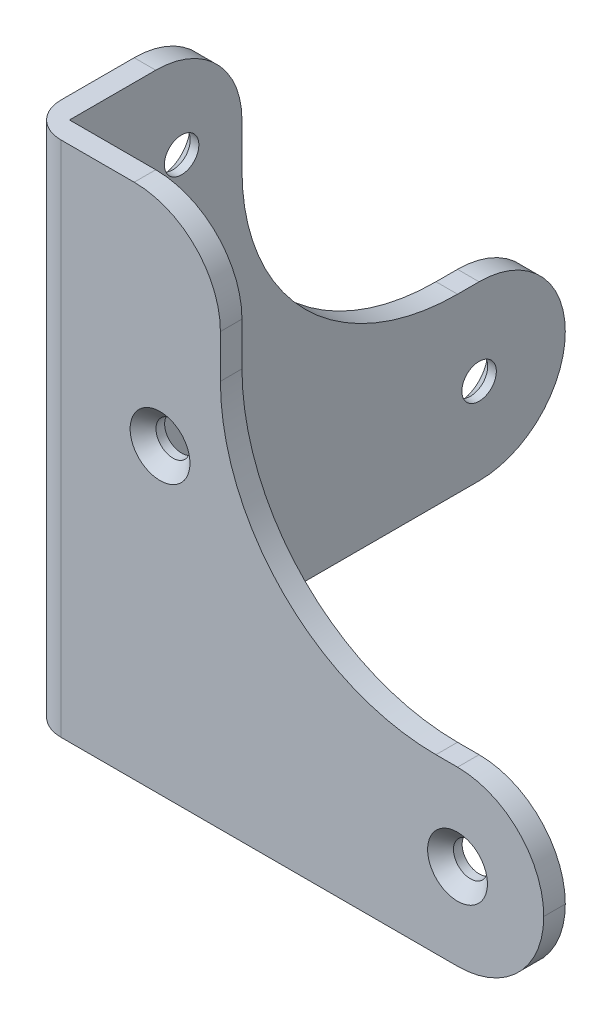
SolidWorks part; units mm, degrees
ref_plane "Front" through (0, 0, 0) normal (0, 0, 1) x (1, 0, 0)
ref_plane "Top" through (0, 0, 0) normal (0, 1, 0) x (1, 0, 0)
ref_plane "Right" through (0, 0, 0) normal (1, 0, 0) x (0, 0, -1)
sketch "Sketch1" plane through (0, 0, 0) normal (0, 1, 0) x (1, 0, 0)
  line L0 (0, 76.2) -> (0, 0)
  line L1 (0, 0) -> (76.2, 0)
  line L2 (76.2, 0) -> (76.2, 3.175)
  line L3 (76.2, 3.175) -> (3.175, 3.175)
  line L4 (3.175, 3.175) -> (3.175, 76.2)
  line L5 (3.175, 76.2) -> (0, 76.2)
  dimension "D1" = 3.175
  dimension "D2" = 76.2
extrude "Boss-Extrude1" add sketch "Sketch1" along normal blind 76.2
sketch "Sketch2" plane through (0, 0, -3.175) normal (0, 0, -1) x (-1, 0, 0)
  line L0 (-76.2, 0) -> (-3.175, 0) construction
  line L1 (-76.2, 76.2) -> (-28.575, 76.2)
  line L2 (-76.2, 76.2) -> (-76.2, 25.4)
  line L3 (-76.2, 25.4) -> (-28.575, 25.4)
  line L4 (-28.575, 76.2) -> (-28.575, 25.4)
  line L5 (-3.175, 76.2) -> (-3.175, 0) construction
  dimension "D1" = 25.4
  dimension "D2" = 25.4
extrude "Cut-Extrude1" cut sketch "Sketch2" against normal through all contours L4 L3 L2 L1
sketch "Sketch3" plane through (3.175, 0, 0) normal (1, 0, 0) x (0, 0, -1)
  line L0 (3.175, 76.2) -> (3.175, 0) construction
  line L1 (76.2, 76.2) -> (28.575, 76.2)
  line L2 (76.2, 76.2) -> (76.2, 25.4)
  line L3 (76.2, 25.4) -> (28.575, 25.4)
  line L4 (28.575, 76.2) -> (28.575, 25.4)
  line L5 (3.175, 0) -> (76.2, 0) construction
  dimension "D1" = 25.4
  dimension "D2" = 25.4
extrude "Cut-Extrude2" cut sketch "Sketch3" against normal through all
fillet "Fillet1" radius 5.08 1 edges at (0, 38.1, 0)
fillet "Fillet2" radius 12.7 6 edges at (1.5875, 76.2, -28.575) (1.5875, 25.4, -76.2) (1.5875, 0, -76.2) (76.2, 0, -1.5875) (76.2, 25.4, -1.5875) (28.575, 76.2, -1.5875)
sketch "Sketch4" plane through (0, 0, 0) normal (0, 0, 1) x (1, 0, 0)
  line L0 (28.575, 63.5) -> (28.575, 25.4) construction
  line L1 (5.08, 76.2) -> (15.875, 76.2) construction
  circle A0 centre (63.5, 12.7) radius 2.5
  arc A1 (76.2, 12.7) -> (63.5, 25.4) centre (63.5, 12.7) ccw construction
  circle A2 centre (19.685, 44.45) radius 2.5
  dimension "D1" = 5
  dimension "D2" = 8.89
  dimension "D3" = 31.75
extrude "Cut-Extrude3" cut sketch "Sketch4" against normal through all
sketch "Sketch5" plane through (0, 0, 0) normal (-1, 0, 0) x (0, 0, 1)
  line L0 (-28.575, 63.5) -> (-28.575, 25.4) construction
  line L1 (-15.875, 76.2) -> (-5.08, 76.2) construction
  circle A0 centre (-63.5, 12.7) radius 2.54
  circle A1 centre (-19.685, 63.5) radius 2.54
  arc A2 (-63.5, 25.4) -> (-76.2, 12.7) centre (-63.5, 12.7) ccw construction
  dimension "D1" = 8.89
  dimension "D2" = 12.7
  dimension "D3" = 5.08
extrude "Cut-Extrude4" cut sketch "Sketch5" against normal through all
chamfer "Chamfer1" distance 1.905 angle 45 4 edges at (66, 12.7, 0) (22.185, 44.45, 0) (0, 63.5, -17.145) (0, 12.7, -60.96)
fillet "Fillet3" radius 31.75 2 edges at (1.5875, 25.4, -28.575) (28.575, 25.4, -1.5875)
